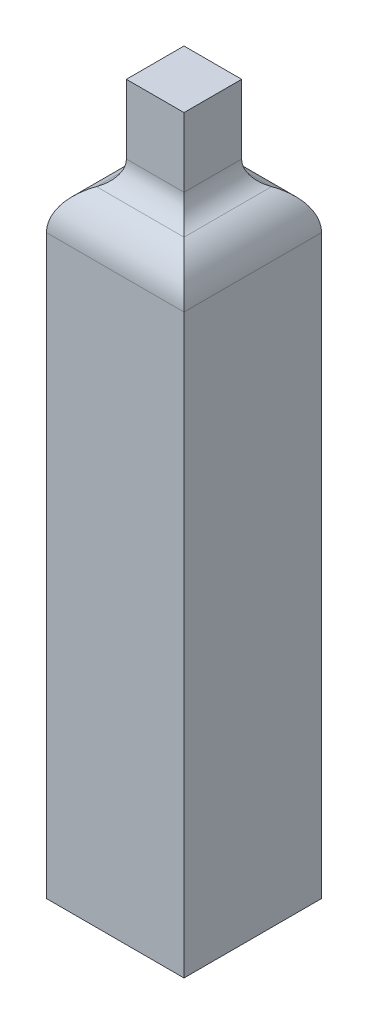
SolidWorks part; units mm, degrees
ref_plane "Front Plane" through (0, 0, 0) normal (0, 0, 1) x (1, 0, 0)
ref_plane "Top Plane" through (0, 0, 0) normal (0, 1, 0) x (1, 0, 0)
ref_plane "Right Plane" through (0, 0, 0) normal (1, 0, 0) x (0, 0, -1)
sketch "Sketch1" plane through (0, 0, 0) normal (0, 1, 0) x (1, 0, 0)
  line L1 (-7.75, 7.75) -> (7.75, 7.75)
  line L2 (-7.75, 7.75) -> (-7.75, -7.75)
  line L3 (-7.75, -7.75) -> (7.75, -7.75)
  line L4 (7.75, 7.75) -> (7.75, -7.75)
  line L5 (-7.75, 7.75) -> (7.75, -7.75) construction
  line L6 (-7.75, -7.75) -> (7.75, 7.75) construction
  point P0 (0, 0)
  dimension "D1" = 15.5
  dimension "D2" = 15.5
extrude "Boss-Extrude1" add sketch "Sketch1" along normal blind 70
sketch "Sketch2" plane through (0, 70, 0) normal (0, 1, 0) x (1, 0, 0)
  line L1 (-3.25, 3.25) -> (3.25, 3.25)
  line L2 (-3.25, 3.25) -> (-3.25, -3.25)
  line L3 (-3.25, -3.25) -> (3.25, -3.25)
  line L4 (3.25, 3.25) -> (3.25, -3.25)
  line L5 (-3.25, 3.25) -> (3.25, -3.25) construction
  line L6 (-3.25, -3.25) -> (3.25, 3.25) construction
  point P0 (0, 0)
  dimension "D1" = 6.5
  dimension "D2" = 6.5
extrude "Boss-Extrude2" add sketch "Sketch2" along normal blind 10
fillet "Fillet1" radius 5 4 edges at (0, 70, -7.75) (7.75, 70, 0) (-7.75, 70, 0) (0, 70, 7.75)
fillet "Fillet2" radius 3 4 edges at (-3.25, 70, 0) (0, 70, -3.25) (0, 70, 3.25) (3.25, 70, 0)
